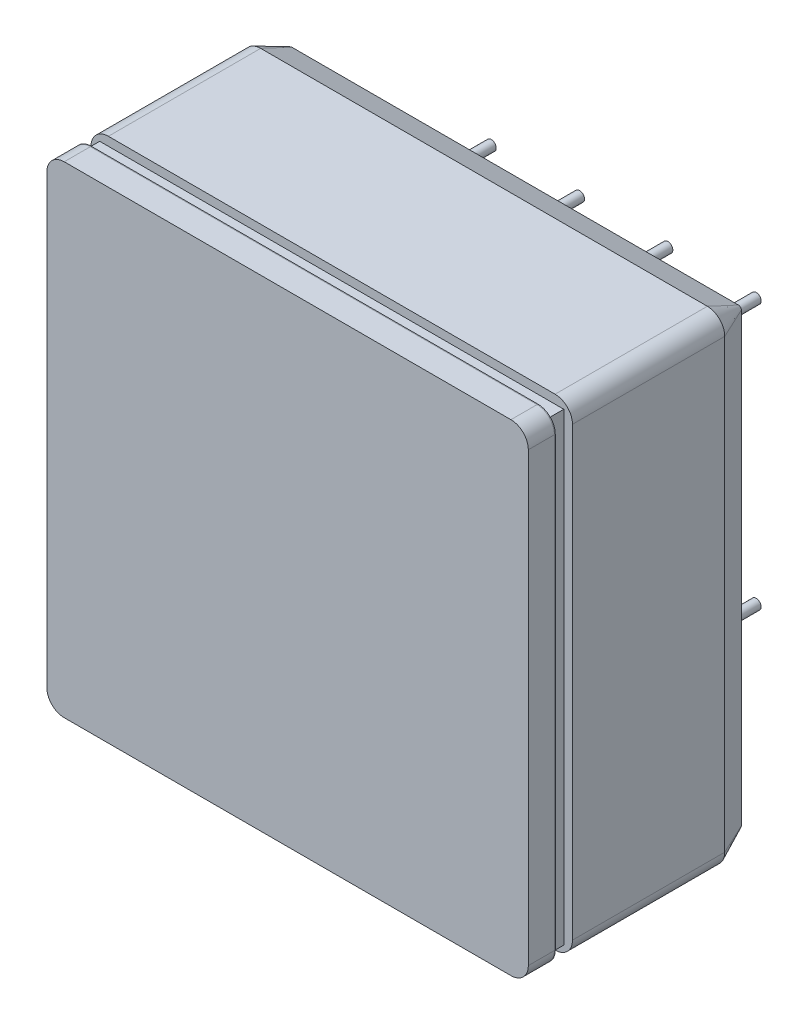
SolidWorks part; units mm, degrees
ref_plane "Front Plane" through (0, 0, 0) normal (0, 0, 1) x (1, 0, 0)
ref_plane "Top Plane" through (0, 0, 0) normal (0, 1, 0) x (1, 0, 0)
ref_plane "Right Plane" through (0, 0, 0) normal (1, 0, 0) x (0, 0, -1)
sketch "Sketch1" plane through (0, 0, 0) normal (0, 0, 1) x (1, 0, 0)
  line L1 (0, 0) -> (27.7, 0) construction
  line L2 (0, 0) -> (0, 27.7) construction
  line L3 (0, 27.7) -> (27.7, 27.7) construction
  line L4 (27.7, 0) -> (27.7, 27.7) construction
  line L5 (0.5, 0.5) -> (27.2, 0.5) construction
  line L6 (0.5, 0.5) -> (0.5, 27.2) construction
  line L7 (0.5, 27.2) -> (27.2, 27.2) construction
  line L8 (27.2, 0.5) -> (27.2, 27.2) construction
  line L9 (2.25, 2.25) -> (25.45, 2.25) construction
  line L10 (2.25, 2.25) -> (2.25, 25.45) construction
  line L11 (2.25, 25.45) -> (25.45, 25.45) construction
  line L12 (25.45, 2.25) -> (25.45, 25.45) construction
  line L13 (3.69, 3.69) -> (24.01, 3.69) construction
  line L14 (3.69, 3.69) -> (3.69, 24.01) construction
  line L15 (3.69, 24.01) -> (24.01, 24.01) construction
  line L16 (24.01, 3.69) -> (24.01, 24.01) construction
ref_plane "Plane1" through (0, 0, -2.54) normal (0, 0, 1) x (1, 0, 0)
sketch "Sketch2" plane through (0, 0, -2.54) normal (0, 0, 1) x (1, 0, 0)
  line L1 (1, 27.7) -> (26.7, 27.7)
  line L2 (0, 26.7) -> (0, 1)
  line L3 (1, 0) -> (26.7, 0)
  line L4 (27.7, 26.7) -> (27.7, 1)
  arc A0 (0, 1) -> (1, 0) centre (1, 1) ccw
  arc A1 (27.7, 1) -> (26.7, 0) centre (26.7, 1) cw
  arc A2 (27.7, 26.7) -> (26.7, 27.7) centre (26.7, 26.7) ccw
  arc A3 (1, 27.7) -> (0, 26.7) centre (1, 26.7) ccw
  dimension "D1" = 1
extrude "metal-case-at-HV" add sketch "Sketch2" against normal blind 8.76
sketch "Sketch3" plane through (0, 0, -2.54) normal (0, 0, 1) x (1, 0, 0)
  line L1 (1.3883, 26.1956) -> (26.126, 26.1956)
  line L2 (1.3883, 26.1956) -> (1.3883, 1.3651)
  line L3 (1.3883, 1.3651) -> (26.126, 1.3651)
  line L4 (26.126, 26.1956) -> (26.126, 1.3651)
extrude "photocathode" add sketch "Sketch3" along normal blind 0.1
sketch "Sketch5" plane through (0, 0, -2.54) normal (0, 0, 1) x (1, 0, 0)
  line L1 (0.5, 27.2) -> (27.2, 27.2)
  line L2 (0.5, 27.2) -> (0.5, 0.5)
  line L3 (0.5, 0.5) -> (27.2, 0.5)
  line L4 (27.2, 27.2) -> (27.2, 0.5)
  line L5 (2.25, 25.45) -> (25.45, 25.45)
  line L6 (2.25, 25.45) -> (2.25, 2.25)
  line L7 (2.25, 2.25) -> (25.45, 2.25)
  line L8 (25.45, 25.45) -> (25.45, 2.25)
extrude "Boss-Extrude3" add sketch "Sketch5" along normal blind 0.99
sketch "Sketch6" plane through (0, 0, -1.55) normal (0, 0, 1) x (1, 0, 0)
  line L1 (1, 27.7) -> (26.7, 27.7)
  line L2 (0, 26.7) -> (0, 1)
  line L3 (1, 0) -> (26.7, 0)
  line L4 (27.7, 26.7) -> (27.7, 1)
  line L5 (2.25, 25.45) -> (25.45, 25.45)
  line L6 (2.25, 25.45) -> (2.25, 2.25)
  line L7 (2.25, 2.25) -> (25.45, 2.25)
  line L8 (25.45, 25.45) -> (25.45, 2.25)
  arc A0 (0, 26.7) -> (1, 27.7) centre (1, 26.7) cw
  arc A1 (0, 1) -> (1, 0) centre (1, 1) ccw
  arc A2 (26.7, 0) -> (27.7, 1) centre (26.7, 1) ccw
  arc A3 (27.7, 26.7) -> (26.7, 27.7) centre (26.7, 26.7) ccw
  point P14 (0, 27.7)
  point P19 (27.7, 0)
  dimension "D1" = 1
  dimension "D2" = 1
extrude "mirrored-surface" add sketch "Sketch6" along normal blind 0.05
sketch "Sketch7" plane through (0, 0, -1.5) normal (0, 0, 1) x (1, 0, 0)
  line L1 (1, 27.7) -> (26.7, 27.7)
  line L2 (0, 26.7) -> (0, 1)
  line L3 (1, 0) -> (26.7, 0)
  line L4 (27.7, 26.7) -> (27.7, 1)
  arc A0 (0, 26.7) -> (1, 27.7) centre (1, 26.7) cw
  arc A1 (27.7, 26.7) -> (26.7, 27.7) centre (26.7, 26.7) ccw
  arc A2 (26.7, 0) -> (27.7, 1) centre (26.7, 1) ccw
  arc A3 (1, 0) -> (0, 1) centre (1, 1) cw
  point P9 (0, 27.7)
  point P13 (27.7, 0)
  dimension "D1" = 1
  dimension "D2" = 1
  dimension "D3" = 1
  dimension "D4" = 1
extrude "front-glass" add sketch "Sketch7" along normal blind 1.5 separate body
sketch "Sketch8" plane through (0, 0, -11.3) normal (0, 0, -1) x (-1, 0, 0)
  circle A0 centre (-24.01, 3.69) radius 0.285
  circle A1 centre (-21.47, 3.69) radius 0.285
  circle A2 centre (-18.93, 3.69) radius 0.285
  circle A3 centre (-16.39, 3.69) radius 0.285
  circle A4 centre (-13.85, 3.69) radius 0.285
  circle A5 centre (-11.31, 3.69) radius 0.285
  circle A6 centre (-8.77, 3.69) radius 0.285
  circle A7 centre (-6.23, 3.69) radius 0.285
  circle A8 centre (-3.69, 3.69) radius 0.285
  circle A9 centre (-24.01, 6.23) radius 0.285
  circle A10 centre (-21.47, 6.23) radius 0.285
  circle A11 centre (-18.93, 6.23) radius 0.285
  circle A12 centre (-16.39, 6.23) radius 0.285
  circle A13 centre (-13.85, 6.23) radius 0.285
  circle A14 centre (-11.31, 6.23) radius 0.285
  circle A15 centre (-8.77, 6.23) radius 0.285
  circle A16 centre (-6.23, 6.23) radius 0.285
  circle A17 centre (-3.69, 6.23) radius 0.285
  circle A18 centre (-24.01, 8.77) radius 0.285
  circle A19 centre (-21.47, 8.77) radius 0.285
  circle A20 centre (-18.93, 8.77) radius 0.285
  circle A21 centre (-16.39, 8.77) radius 0.285
  circle A22 centre (-13.85, 8.77) radius 0.285
  circle A23 centre (-11.31, 8.77) radius 0.285
  circle A24 centre (-8.77, 8.77) radius 0.285
  circle A25 centre (-6.23, 8.77) radius 0.285
  circle A26 centre (-3.69, 8.77) radius 0.285
  circle A27 centre (-24.01, 11.31) radius 0.285
  circle A28 centre (-21.47, 11.31) radius 0.285
  circle A29 centre (-18.93, 11.31) radius 0.285
  circle A30 centre (-16.39, 11.31) radius 0.285
  circle A31 centre (-13.85, 11.31) radius 0.285
  circle A32 centre (-11.31, 11.31) radius 0.285
  circle A33 centre (-8.77, 11.31) radius 0.285
  circle A34 centre (-6.23, 11.31) radius 0.285
  circle A35 centre (-3.69, 11.31) radius 0.285
  circle A36 centre (-24.01, 13.85) radius 0.285
  circle A37 centre (-21.47, 13.85) radius 0.285
  circle A38 centre (-18.93, 13.85) radius 0.285
  circle A39 centre (-16.39, 13.85) radius 0.285
  circle A40 centre (-13.85, 13.85) radius 0.285
  circle A41 centre (-11.31, 13.85) radius 0.285
  circle A42 centre (-8.77, 13.85) radius 0.285
  circle A43 centre (-6.23, 13.85) radius 0.285
  circle A44 centre (-3.69, 13.85) radius 0.285
  circle A45 centre (-24.01, 16.39) radius 0.285
  circle A46 centre (-21.47, 16.39) radius 0.285
  circle A47 centre (-18.93, 16.39) radius 0.285
  circle A48 centre (-16.39, 16.39) radius 0.285
  circle A49 centre (-13.85, 16.39) radius 0.285
  circle A50 centre (-11.31, 16.39) radius 0.285
  circle A51 centre (-8.77, 16.39) radius 0.285
  circle A52 centre (-6.23, 16.39) radius 0.285
  circle A53 centre (-3.69, 16.39) radius 0.285
  circle A54 centre (-24.01, 18.93) radius 0.285
  circle A55 centre (-21.47, 18.93) radius 0.285
  circle A56 centre (-18.93, 18.93) radius 0.285
  circle A57 centre (-16.39, 18.93) radius 0.285
  circle A58 centre (-13.85, 18.93) radius 0.285
  circle A59 centre (-11.31, 18.93) radius 0.285
  circle A60 centre (-8.77, 18.93) radius 0.285
  circle A61 centre (-6.23, 18.93) radius 0.285
  circle A62 centre (-3.69, 18.93) radius 0.285
  circle A63 centre (-24.01, 21.47) radius 0.285
  circle A64 centre (-21.47, 21.47) radius 0.285
  circle A65 centre (-18.93, 21.47) radius 0.285
  circle A66 centre (-16.39, 21.47) radius 0.285
  circle A67 centre (-13.85, 21.47) radius 0.285
  circle A68 centre (-11.31, 21.47) radius 0.285
  circle A69 centre (-8.77, 21.47) radius 0.285
  circle A70 centre (-6.23, 21.47) radius 0.285
  circle A71 centre (-3.69, 21.47) radius 0.285
  circle A72 centre (-24.01, 24.01) radius 0.285
  circle A73 centre (-21.47, 24.01) radius 0.285
  circle A74 centre (-18.93, 24.01) radius 0.285
  circle A75 centre (-16.39, 24.01) radius 0.285
  circle A76 centre (-13.85, 24.01) radius 0.285
  circle A77 centre (-11.31, 24.01) radius 0.285
  circle A78 centre (-8.77, 24.01) radius 0.285
  circle A79 centre (-6.23, 24.01) radius 0.285
  circle A80 centre (-3.69, 24.01) radius 0.285
extrude "pins" add sketch "Sketch8" along normal blind 5.5
sketch "Sketch9" plane through (0, 0, -16.8) normal (0, 0, -1) x (-1, 0, 0)
  line L0 (-22.1816, 24.8612) -> (-20.7784, 24.8612)
  line L1 (-22.1816, 24.8612) -> (-22.1816, 23.3649)
  line L2 (-22.1816, 23.3649) -> (-20.7784, 23.3649)
  line L3 (-20.7784, 24.8612) -> (-20.7784, 23.3649)
  line L4 (-17.3107, 24.8612) -> (-15.8078, 24.8612)
  line L5 (-17.3107, 24.8612) -> (-17.3107, 22.981)
  line L6 (-17.3107, 22.981) -> (-15.8078, 22.981)
  line L7 (-15.8078, 24.8612) -> (-15.8078, 22.981)
  line L8 (-11.8655, 24.8612) -> (-10.4335, 24.8612)
  line L9 (-11.8655, 24.8612) -> (-11.8655, 22.981)
  line L10 (-11.8655, 22.981) -> (-10.4335, 22.981)
  line L11 (-10.4335, 24.8612) -> (-10.4335, 22.981)
  line L12 (-7.2079, 24.8612) -> (-2.98, 24.8612)
  line L13 (-7.2079, 24.8612) -> (-7.2079, 23.3649)
  line L14 (-7.2079, 23.3649) -> (-2.98, 23.3649)
  line L15 (-2.98, 24.8612) -> (-2.98, 23.3649)
  line L16 (-24.8835, 22.2271) -> (-23.0472, 22.2271)
  line L17 (-24.8835, 22.2271) -> (-24.8835, 10.532)
  line L18 (-24.8835, 10.532) -> (-23.0472, 10.532)
  line L19 (-23.0472, 22.2271) -> (-23.0472, 10.532)
  line L20 (-24.8835, 7.577) -> (-23.0472, 7.577)
  line L21 (-24.8835, 7.577) -> (-24.8835, 2.706)
  line L22 (-24.8835, 2.706) -> (-23.0472, 2.706)
  line L23 (-23.0472, 7.577) -> (-23.0472, 2.706)
  line L24 (-19.7935, 22.4499) -> (-17.9649, 22.4499)
  line L25 (-19.7935, 22.4499) -> (-19.7935, 20.7304)
  line L26 (-19.7935, 20.7304) -> (-17.9649, 20.7304)
  line L27 (-17.9649, 22.4499) -> (-17.9649, 20.7304)
  line L28 (-14.5667, 22.4499) -> (-12.9507, 22.4499)
  line L29 (-14.5667, 22.4499) -> (-14.5667, 20.7304)
  line L30 (-14.5667, 20.7304) -> (-12.9507, 20.7304)
  line L31 (-12.9507, 22.4499) -> (-12.9507, 20.7304)
  line L32 (-9.3756, 22.4499) -> (-8.0103, 22.4499)
  line L33 (-9.3756, 22.4499) -> (-9.3756, 20.7304)
  line L34 (-9.3756, 20.7304) -> (-8.0103, 20.7304)
  line L35 (-8.0103, 22.4499) -> (-8.0103, 20.7304)
  line L36 (-4.5054, 22.2271) -> (-2.98, 22.2271)
  line L37 (-4.5054, 22.2271) -> (-4.5054, 20.7304)
  line L38 (-4.5054, 20.7304) -> (-2.98, 20.7304)
  line L39 (-2.98, 22.2271) -> (-2.98, 20.7304)
  line L40 (-22.4238, 19.8145) -> (-5.3688, 19.8145)
  line L41 (-22.4238, 19.8145) -> (-22.4238, 18.3702)
  line L42 (-22.4238, 18.3702) -> (-5.3688, 18.3702)
  line L43 (-5.3688, 19.8145) -> (-5.3688, 18.3702)
  line L44 (-22.4238, 14.7607) -> (-5.3688, 14.7607)
  line L45 (-22.4238, 14.7607) -> (-22.4238, 13.143)
  line L46 (-22.4238, 13.143) -> (-5.3688, 13.143)
  line L47 (-5.3688, 14.7607) -> (-5.3688, 13.143)
  line L48 (-22.4238, 9.6389) -> (-5.3688, 9.6389)
  line L49 (-22.4238, 9.6389) -> (-22.4238, 8.1251)
  line L50 (-22.4238, 8.1251) -> (-5.3688, 8.1251)
  line L51 (-5.3688, 9.6389) -> (-5.3688, 8.1251)
  line L52 (-4.5054, 17.5985) -> (-2.98, 17.5985)
  line L53 (-4.5054, 17.5985) -> (-4.5054, 2.706)
  line L54 (-4.5054, 2.706) -> (-2.98, 2.706)
  line L55 (-2.98, 17.5985) -> (-2.98, 2.706)
  line L56 (-19.7935, 17.3274) -> (-17.9649, 17.3274)
  line L57 (-19.7935, 17.3274) -> (-19.7935, 15.6815)
  line L58 (-19.7935, 15.6815) -> (-17.9649, 15.6815)
  line L59 (-17.9649, 17.3274) -> (-17.9649, 15.6815)
  line L60 (-14.5667, 17.3274) -> (-12.9507, 17.3274)
  line L61 (-14.5667, 17.3274) -> (-14.5667, 15.6815)
  line L62 (-14.5667, 15.6815) -> (-12.9507, 15.6815)
  line L63 (-12.9507, 17.3274) -> (-12.9507, 15.6815)
  line L64 (-9.3756, 17.3274) -> (-8.0103, 17.3274)
  line L65 (-9.3756, 17.3274) -> (-9.3756, 15.6815)
  line L66 (-9.3756, 15.6815) -> (-8.0103, 15.6815)
  line L67 (-8.0103, 17.3274) -> (-8.0103, 15.6815)
  line L68 (-9.3756, 12.3613) -> (-8.0103, 12.3613)
  line L69 (-9.3756, 12.3613) -> (-9.3756, 10.532)
  line L70 (-9.3756, 10.532) -> (-8.0103, 10.532)
  line L71 (-8.0103, 12.3613) -> (-8.0103, 10.532)
  line L72 (-9.3756, 7.021) -> (-8.2349, 7.021)
  line L73 (-9.3756, 7.021) -> (-9.3756, 5.5289)
  line L74 (-9.3756, 5.5289) -> (-8.2349, 5.5289)
  line L75 (-8.2349, 7.021) -> (-8.2349, 5.5289)
  line L76 (-14.9745, 7.021) -> (-13.2505, 7.021)
  line L77 (-14.9745, 7.021) -> (-14.9745, 5.5289)
  line L78 (-14.9745, 5.5289) -> (-13.2505, 5.5289)
  line L79 (-13.2505, 7.021) -> (-13.2505, 5.5289)
  line L80 (-14.5667, 12.1026) -> (-13.2505, 12.1026)
  line L81 (-14.5667, 12.1026) -> (-14.5667, 10.532)
  line L82 (-14.5667, 10.532) -> (-13.2505, 10.532)
  line L83 (-13.2505, 12.1026) -> (-13.2505, 10.532)
  line L84 (-19.7935, 12.3613) -> (-18.2001, 12.3613)
  line L85 (-19.7935, 12.3613) -> (-19.7935, 10.532)
  line L86 (-19.7935, 10.532) -> (-18.2001, 10.532)
  line L87 (-18.2001, 12.3613) -> (-18.2001, 10.532)
  line L88 (-19.7935, 7.021) -> (-17.9649, 7.021)
  line L89 (-19.7935, 7.021) -> (-19.7935, 5.5289)
  line L90 (-19.7935, 5.5289) -> (-17.9649, 5.5289)
  line L91 (-17.9649, 7.021) -> (-17.9649, 5.5289)
  line L92 (-22.4238, 4.9123) -> (-20.5348, 4.9123)
  line L93 (-22.4238, 4.9123) -> (-22.4238, 2.706)
  line L94 (-22.4238, 2.706) -> (-20.5348, 2.706)
  line L95 (-20.5348, 4.9123) -> (-20.5348, 2.706)
  line L96 (-17.3107, 4.4899) -> (-10.4335, 4.4899)
  line L97 (-17.3107, 4.4899) -> (-17.3107, 2.706)
  line L98 (-17.3107, 2.706) -> (-10.4335, 2.706)
  line L99 (-10.4335, 4.4899) -> (-10.4335, 2.706)
  line L100 (-7.5372, 4.4899) -> (-5.7773, 4.4899)
  line L101 (-7.5372, 4.4899) -> (-7.5372, 3.0088)
  line L102 (-7.5372, 3.0088) -> (-5.7773, 3.0088)
  line L103 (-5.7773, 4.4899) -> (-5.7773, 3.0088)
extrude "Cut-Extrude1" cut sketch "Sketch9" against normal blind 5.5
sketch "Sketch10" plane through (0, 0, -11.3) normal (0, 0, -1) x (-1, 0, 0)
  line L1 (-26.7, 27.7) -> (-1, 27.7)
  line L2 (-27.7, 26.7) -> (-27.7, 1)
  line L3 (-26.7, 0) -> (-1, 0)
  line L4 (0, 26.7) -> (0, 1)
  arc A0 (-26.7, 0) -> (-27.7, 1) centre (-26.7, 1) cw
  arc A1 (0, 26.7) -> (-1, 27.7) centre (-1, 26.7) ccw
  arc A2 (0, 1) -> (-1, 0) centre (-1, 1) cw
  arc A3 (-27.7, 26.7) -> (-26.7, 27.7) centre (-26.7, 26.7) cw
  point P11 (0, 0)
  dimension "D1" = 1
extrude "rubber" add sketch "Sketch10" along normal blind 1.79 draft 25 separate body
sketch "Sketch11" plane through (0, 0, -16.8) normal (0, 0, -1) x (-1, 0, 0)
  line L1 (-26.7, 27.7) -> (-1, 27.7) construction
  line L2 (-27.7, 26.7) -> (-27.7, 1) construction
  line L3 (-26.7, 0) -> (-1, 0) construction
  line L4 (0, 26.7) -> (0, 1) construction
  circle A0 centre (-24.01, 24.01) radius 0.285
  circle A1 centre (-18.93, 24.01) radius 0.285
  circle A2 centre (-13.85, 24.01) radius 0.285
  circle A3 centre (-8.77, 24.01) radius 0.285
  circle A4 centre (-6.23, 21.47) radius 0.285
  circle A5 centre (-11.31, 21.47) radius 0.285
  circle A6 centre (-16.39, 21.47) radius 0.285
  circle A7 centre (-21.47, 21.47) radius 0.285
  circle A8 centre (-21.47, 16.39) radius 0.285
  circle A9 centre (-16.39, 16.39) radius 0.285
  circle A10 centre (-11.31, 16.39) radius 0.285
  circle A11 centre (-6.23, 16.39) radius 0.285
  circle A12 centre (-3.69, 18.93) radius 0.285
  circle A13 centre (-21.47, 11.31) radius 0.285
  circle A14 centre (-16.39, 11.31) radius 0.285
  circle A15 centre (-11.31, 11.31) radius 0.285
  circle A16 centre (-6.23, 11.31) radius 0.285
  circle A17 centre (-24.01, 8.77) radius 0.285
  circle A18 centre (-21.47, 6.23) radius 0.285
  arc A19 (-26.7, 27.7) -> (-27.7, 26.7) centre (-26.7, 26.7) ccw construction
  circle A20 centre (-11.31, 6.23) radius 0.285
  circle A21 centre (-6.23, 6.23) radius 0.285
  circle A22 centre (-8.77, 3.69) radius 0.285
  circle A23 centre (-18.93, 3.69) radius 0.285
  circle A24 centre (-16.39, 6.23) radius 0.285
  arc A25 (-27.7, 1) -> (-26.7, 0) centre (-26.7, 1) ccw construction
  arc A26 (0, 1) -> (-1, 0) centre (-1, 1) cw construction
  arc A27 (0, 26.7) -> (-1, 27.7) centre (-1, 26.7) ccw construction
  dimension "D1" = 1
  dimension "D2" = 1
ref_axis "corner-pin" through (24.01, 24.01, -16.8) along (0, 0, 1)
ref_axis "anode04" through (6.23, 6.23, -16.8) along (0, 0, 1)
ref_axis "anode13" through (21.47, 21.47, -16.8) along (0, 0, 1)
